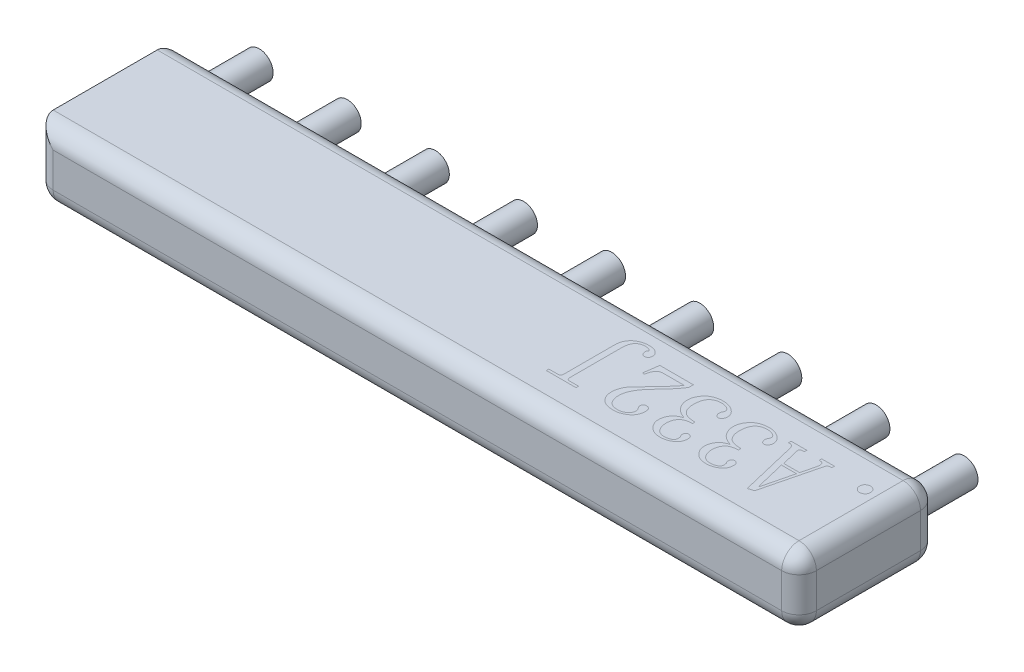
SolidWorks part; units mm, degrees
ref_plane "前视基准面" through (0, 0, 0) normal (0, 0, 1) x (1, 0, 0)
ref_plane "上视基准面" through (0, 0, 0) normal (0, 1, 0) x (1, 0, 0)
ref_plane "右视基准面" through (0, 0, 0) normal (1, 0, 0) x (0, 0, -1)
sketch "草图1" plane through (0, 0, 0) normal (0, 0, 1) x (1, 0, 0)
  line L0 (0, 0) -> (22, 0)
  line L1 (22, 0) -> (22, 2)
  line L2 (22, 2) -> (0, 2)
  line L3 (0, 2) -> (0, 0)
  dimension "D1" = 2
  dimension "D2" = 22
extrude "凸台-拉伸1" add sketch "草图1" along normal blind 4
fillet "圆角1" radius 0.5 11 edges at (0, 1, 0) (0, 1, 4) (22, 1, 0) (22, 1, 4) (22, 2, 2) (22, 0, 2) (0, 0, 2) (11, 0, 0) (11, 2, 0) (11, 0, 4) (11, 2, 4)
sketch "草图2" plane through (0, 0, 0) normal (0, 0, -1) x (-1, 0, 0)
  line L0 (-11, 0.5) -> (-11, 5.8262) construction
  line L1 (-21.5, 0.5) -> (-0.5, 0.5) construction
  line L2 (-21.5, 1) -> (-0.5, 1) construction
  line L3 (-21.5, 1.5) -> (-21.5, 0.5) construction
  line L4 (-0.5, 0.5) -> (-0.5, 1.5) construction
  circle A0 centre (-11, 1) radius 0.4
  circle A1 centre (-8.46, 1) radius 0.4
  circle A2 centre (-5.92, 1) radius 0.4
  circle A3 centre (-3.38, 1) radius 0.4
  circle A4 centre (-0.84, 1) radius 0.4
  circle A5 centre (-13.54, 1) radius 0.4
  circle A6 centre (-16.08, 1) radius 0.4
  circle A7 centre (-18.62, 1) radius 0.4
  circle A8 centre (-21.16, 1) radius 0.4
  dimension "D1" = 5
  dimension "D2" = 5
extrude "凸台-拉伸2" add sketch "草图2" along normal blind 1.6
sketch "草图3" plane through (0, 2, 0) normal (0, 1, 0) x (-1, 0, 0)
  line L0 (-21.5, 1.0824) -> (0, 1.0824) construction
  line L1 (-21.5, 3.5) -> (-21.5, 0.5) construction
  line L2 (0, 3.5) -> (0, 0.5) construction
  text T0 ".A332J" height in points 5
wrap "包覆1" sketch "草图3" wrap type scribe source sketch "草图3" face at (10.75, 2, 2)
